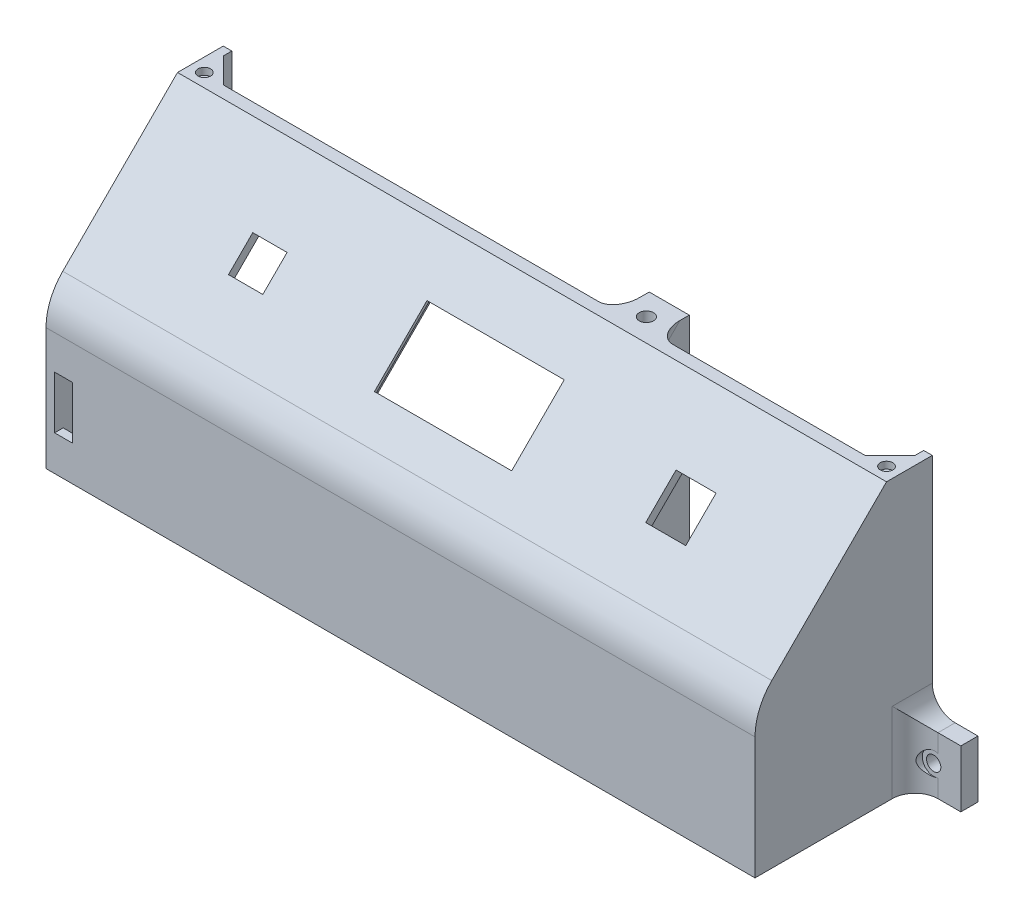
SolidWorks part; units mm, degrees
ref_plane "Front Plane" through (0, 0, 0) normal (0, 0, 1) x (1, 0, 0)
ref_plane "Top Plane" through (0, 0, 0) normal (0, 1, 0) x (1, 0, 0)
ref_plane "Right Plane" through (0, 0, 0) normal (1, 0, 0) x (0, 0, -1)
sketch "Sketch1" plane through (0, 0, 0) normal (0, 1, 0) x (1, 0, 0)
  line L1 (0, 31) -> (124, 31)
  line L2 (0, 31) -> (0, 0)
  line L3 (0, 0) -> (124, 0)
  line L4 (124, 31) -> (124, 0)
  dimension "D1" = 124
  dimension "30" = 31
extrude "Boss-Extrude1" add sketch "Sketch1" along normal blind 50
sketch "Sketch2" plane through (0, 0, 0) normal (-1, 0, 0) x (0, 0, 1)
  line L0 (-23, 48.5) -> (0, 25.5)
  line L2 (0, 50) -> (0, 0) construction
  line L3 (0, 25.5) -> (0, 50)
  line L5 (-31, 50) -> (-31, 0) construction
  line L7 (-31, 50) -> (0, 50)
  line L8 (-31, 50) -> (-31, 48.5)
  line L9 (-31, 48.5) -> (-23, 48.5)
  dimension "D1" = 45
  dimension "D2" = 1.5
  dimension "D4" = 8
extrude "Cut-Extrude1" cut sketch "Sketch2" against normal through all
ref_plane "Plane1" through (1.5, 0, 0) normal (-1, 0, 0) x (0, 0, 1)
sketch "Sketch3" plane through (1.5, 0, 0) normal (-1, 0, 0) x (0, 0, 1)
  line L0 (-31, 48.5) -> (-25.1213, 48.5)
  line L1 (-31, 48.5) -> (-31, 0) construction
  line L3 (-1.5, 24.8787) -> (-1.5, 1.5)
  line L4 (-1.5, 1.5) -> (-31, 1.5)
  line L5 (-31, 1.5) -> (-31, 48.5)
  line L6 (-31, 48.5) -> (-23, 48.5) construction
  line L8 (0, 25.5) -> (0, 0) construction
  line L9 (-31, 0) -> (0, 0) construction
  line L12 (-23, 48.5) -> (0, 25.5) construction
  line L14 (-23, 48.5) -> (0, 25.5) construction
  line L15 (-25.1213, 48.5) -> (-1.5, 24.8787)
  dimension "D1" = 1.5
  dimension "D3" = 1.5
  dimension "D4" = 1.5
extrude "Cut-Extrude2" cut sketch "Sketch3" against normal blind 121
sketch "Sketch4" plane through (0, 1.5, 0) normal (0, 1, 0) x (1, 0, 0)
  line L0 (84, 24) -> (84, 1.5)
  line L1 (122.5, 1.5) -> (1.5, 1.5) construction
  line L4 (122.5, 24) -> (84, 24)
  line L5 (84, 1.5) -> (81.5, 1.5)
  line L6 (81.5, 1.5) -> (81.5, 26.5)
  line L7 (81.5, 26.5) -> (122.5, 26.5)
  line L10 (8, 22) -> (1.5, 22) construction
  line L11 (60, 13.5) -> (60, 22)
  line L12 (60, 22) -> (29.5, 22)
  line L15 (27, 22) -> (27, 24.5)
  line L16 (27, 24.5) -> (62.5, 24.5)
  line L17 (62.5, 24.5) -> (62.5, 13.5)
  line L19 (29.5, 22) -> (27, 22)
  line L20 (60, 13.5) -> (62.5, 13.5)
  line L21 (1.5, 31) -> (1.5, 1.5) construction
  line L22 (29.5, 6.5) -> (27, 6.5)
  line L23 (29.5, 6.5) -> (29.5, 1.5)
  line L24 (29.5, 1.5) -> (27, 1.5)
  line L25 (27, 6.5) -> (27, 1.5)
  line L26 (62.5, 13.5) -> (81.5, 13.5) construction
  line L27 (27, 22) -> (8, 22) construction
  line L29 (122.5, 24) -> (122.5, 26.5)
  line L31 (122.5, 31) -> (122.5, 1.5) construction
  dimension "D1" = 2.5
  dimension "D2" = 2.5
  dimension "D3" = 38.5
  dimension "D4" = 22.5
  dimension "D5" = 6.5
  dimension "D6" = 30.5
  dimension "D7" = 20.5
  dimension "D8" = 2.5
  dimension "D9" = 2.5
  dimension "D10" = 12
  dimension "D11" = 2.5
  dimension "D12" = 5
  dimension "D13" = 2.5
extrude "Boss-Extrude2" add sketch "Sketch4" along normal blind 5
sketch "Sketch5" plane through (0, 12.75, 12.75) normal (0, 0.7071, 0.7071) x (1, 0, 0)
  line L0 (74, 28.5581) -> (124, 28.5581) construction
  line L1 (50, 41.5581) -> (74, 41.5581)
  line L2 (50, 41.5581) -> (50, 28.5581)
  line L3 (50, 28.5581) -> (74, 28.5581)
  line L4 (74, 41.5581) -> (74, 28.5581)
  line L5 (124, 50.5581) -> (124, 18.0312) construction
  line L6 (50, 28.5581) -> (0, 28.5581) construction
  line L7 (0, 50.5581) -> (0, 18.0312) construction
  line L8 (0, 50.5581) -> (0, 18.0312) construction
  line L9 (124, 50.5581) -> (0, 50.5581) construction
  line L14 (95.5, 31.3081) -> (102.5, 38.8081) construction
  line L19 (95.5, 38.8081) -> (102.5, 38.8081)
  line L20 (95.5, 38.8081) -> (95.5, 31.3081)
  line L21 (95.5, 31.3081) -> (102.5, 31.3081)
  line L22 (102.5, 38.8081) -> (102.5, 31.3081)
  line L23 (22, 32.0581) -> (28, 38.0581) construction
  line L24 (22, 38.0581) -> (28, 38.0581)
  line L25 (22, 38.0581) -> (22, 32.0581)
  line L26 (22, 32.0581) -> (28, 32.0581)
  line L27 (28, 38.0581) -> (28, 32.0581)
  line L28 (25, 35.0581) -> (50, 35.0581) construction
  line L29 (99, 35.0581) -> (74, 35.0581) construction
  line L30 (25, 35.0581) -> (0, 35.0581) construction
  point P22 (99, 35.0581)
  point P25 (25, 35.0581)
  point P26 (50, 35.0581)
  dimension "D3" = 6.5
  dimension "D4" = 6
  dimension "D6" = 7.5
  dimension "D1" = 24
  dimension "D2" = 13
  dimension "D5" = 6
  dimension "D7" = 7
  dimension "D8" = 9
extrude "Cut-Extrude3" cut sketch "Sketch5" against normal blind 4
sketch "Sketch6" plane through (0, 1.5, 0) normal (0, 1, 0) x (1, 0, 0)
  line L0 (27, 1.5) -> (1.5, 1.5) construction
  line L1 (9.4, 1.5) -> (5.9, 1.5)
  line L2 (9.4, 1.5) -> (9.4, 20.5)
  line L3 (9.4, 20.5) -> (5.9, 20.5)
  line L4 (5.9, 1.5) -> (5.9, 20.5)
  line L5 (1.5, 31) -> (1.5, 1.5) construction
  dimension "D1" = 3.5
  dimension "D2" = 4.4
  dimension "D3" = 19
extrude "Boss-Extrude3" add sketch "Sketch6" along normal blind 3.5
sketch "Sketch8" plane through (0, 5, 0) normal (0, 1, 0) x (1, 0, 0)
  line L0 (9.4, 1.5) -> (9.4, 20.5) construction
  line L1 (9.4, 9.5) -> (7.2, 9.5)
  line L2 (9.4, 9.5) -> (9.4, 18.5)
  line L3 (9.4, 18.5) -> (7.2, 18.5)
  line L4 (7.2, 9.5) -> (7.2, 18.5)
  line L5 (5.9, 1.5) -> (9.4, 1.5) construction
  dimension "D1" = 8
  dimension "D2" = 17
  dimension "D3" = 2.2
extrude "Boss-Extrude4" add sketch "Sketch8" along normal blind 8
fillet "Fillet1" radius 3 9 edges at (81.5, 1.5, -14) (27, 1.5, -4) (27, 1.5, -23.25) (44.75, 1.5, -24.5) (62.5, 1.5, -19) (102, 1.5, -26.5) (9.4, 1.5, -11) (8.3, 5, -9.5) (8.3, 5, -18.5)
sketch "Sketch7" plane through (0, 0, -1.5) normal (0, 0, -1) x (-1, 0, 0)
  line L0 (-1.5, -17.05) -> (-1.5, 17.05) construction
  line L1 (-4.6, 15.37) -> (-1.5, 15.37)
  line L2 (-4.6, 15.37) -> (-4.6, 6.17)
  line L3 (-4.6, 6.17) -> (-1.5, 6.17)
  line L4 (-1.5, 15.37) -> (-1.5, 6.17)
  line L5 (-122.5, 1.5) -> (-1.5, 1.5) construction
  dimension "D1" = 3.1
  dimension "D2" = 9.2
  dimension "D3" = 4.67
extrude "Cut-Extrude4" cut sketch "Sketch7" against normal blind 8
sketch "Sketch10" plane through (0, 0, -31) normal (0, 0, -1) x (-1, 0, 0)
  line L1 (-124, 10) -> (-132, 10)
  line L2 (-124, 10) -> (-124, 0)
  line L3 (-124, 0) -> (-132, 0)
  line L4 (-132, 10) -> (-132, 0)
  line L5 (0, 0) -> (8, 0)
  line L6 (0, 0) -> (0, 10)
  line L7 (0, 10) -> (8, 10)
  line L8 (8, 0) -> (8, 10)
  line L9 (-124, 0) -> (0, 0) construction
  dimension "D1" = 8
  dimension "D2" = 8
  dimension "D3" = 10
extrude "Boss-Extrude5" add sketch "Sketch10" against normal blind 3
fillet "Fillet4" radius 4 4 edges at (0, 5, -28) (124, 5, -28) (0, 10, -29.5) (124, 10, -29.5)
sketch "Sketch13" plane through (0, 0, -31) normal (0, 0, -1) x (-1, 0, 0)
  line L3 (-130.5, 8.5) -> (-124, 1.5) construction
  line L7 (0, 14) -> (0, 1.5) construction
  line L8 (6.5, 8.5) -> (0, 1.5) construction
  line L9 (8, 0) -> (8, 10) construction
  line L10 (8, 10) -> (4, 10) construction
  line L12 (-132, 0) -> (8, 0) construction
  line L14 (-122.5, 48.5) -> (-122.5, 1.5) construction
  line L15 (-128, 10) -> (-132, 10) construction
  line L16 (-132, 10) -> (-132, 0) construction
  circle A0 centre (3.25, 5) radius 1.25
  circle A1 centre (-127.25, 5) radius 1.25
  dimension "D3" = 2.5
  dimension "D9" = 2.5
  dimension "D1" = 1.5
  dimension "D2" = 1.5
  dimension "D4" = 1.5
  dimension "D5" = 1.5
  dimension "D6" = 1.5
  dimension "D7" = 1.5
  dimension "D8" = 1.5
extrude "Cut-Extrude6" cut sketch "Sketch13" against normal blind 5
sketch "Sketch14" plane through (0, 0, -28) normal (0, 0, 1) x (1, 0, 0)
  arc A0 (-4, 6) -> (-4, 4) centre (-3.25, 5) ccw construction
  arc A1 (-4, 6) -> (-4, 4) centre (-3.25, 5) ccw construction
  circle A2 centre (-3.25, 5) radius 2
  arc A3 (128, 4) -> (128, 6) centre (127.25, 5) ccw construction
  arc A4 (128, 4) -> (128, 6) centre (127.25, 5) ccw construction
  circle A5 centre (127.25, 5) radius 2
  dimension "D1" = 4
  dimension "D2" = 4
extrude "Cut-Extrude7" cut sketch "Sketch14" along normal blind 5
sketch "Sketch17" plane through (0, 1.5, 0) normal (0, 1, 0) x (1, 0, 0)
  line L4 (74.5, 24) -> (74.5, 31)
  line L5 (81.5, 26.5) -> (81.5, 1.5) construction
  line L6 (122.5, 31) -> (1.5, 31) construction
  line L7 (81.5, 24) -> (74.5, 24)
  line L8 (81.5, 24) -> (81.5, 31)
  line L9 (81.5, 31) -> (74.5, 31)
  line L11 (62.5, 13.5) -> (62.5, 24.5) construction
  line L12 (81.5, 26.5) -> (81.5, 1.5) construction
  line L13 (62.5, 13.5) -> (62.5, 24.5) construction
  line L14 (124, 24) -> (0, 24) construction
  dimension "D1" = 7
  dimension "D2" = 7
extrude "Boss-Extrude7" add sketch "Sketch17" along normal through all
sketch "Sketch18" plane through (0, 48.5, 0) normal (0, 1, 0) x (1, 0, 0)
  line L0 (81.5, 25.1213) -> (81.5, 31) construction
  line L1 (124, 23) -> (0, 23) construction
  line L2 (81.5, 31) -> (74.5, 31) construction
  line L3 (81.5, 25.1213) -> (81.5, 31) construction
  line L4 (124, 23) -> (0, 23) construction
  line L5 (81.5, 31) -> (74.5, 31) construction
  line L6 (74.5, 31) -> (81.5, 23) construction
  line L7 (81.5, 25.1213) -> (81.5, 23) construction
  circle A0 centre (78, 27) radius 1.25
  dimension "D1" = 2.5
extrude "Cut-Extrude9" cut sketch "Sketch18" against normal blind 5
fillet "Fillet5" radius 3 6 edges at (74.5, 47.9393, -24.5607) (81.5, 47.9393, -24.5607) (81.5, 5.5, -24) (80.6213, 2.3787, -24) (76.5, 1.5, -24) (74.5, 1.5, -27.5)
fillet "Fillet6" radius 10 1 edges at (62, 25.5, 0)
fillet "Fillet8" radius 3 2 edges at (62, 24.8787, -1.5) (122.5, 36.6893, -13.3107)
sketch "Sketch19" plane through (0, 11.6893, 11.6893) normal (0, -0.7071, -0.7071) x (1, 0, 0)
  line L0 (74, -41.5581) -> (50, -41.5581) construction
  line L1 (74.5, -41.5581) -> (68, -41.5581)
  line L2 (74.5, -41.5581) -> (74.5, -24.5581)
  line L3 (74.5, -24.5581) -> (68.5, -24.5581)
  line L4 (49.5, -41.5581) -> (49.5, -24.5581)
  line L5 (74, -28.5581) -> (74.5, -24.5581) construction
  line L6 (50, -28.5581) -> (49.5, -24.5581) construction
  line L7 (68.5, -24.5581) -> (68.5, -19.8952)
  line L9 (55.5, -19.8952) -> (55.5, -24.5581)
  line L10 (55.5, -24.5581) -> (49.5, -24.5581)
  line L12 (55.5, -19.8952) -> (68.5, -19.8952)
  line L13 (68, -41.5581) -> (68, -46.5581)
  line L14 (68, -46.5581) -> (56, -46.5581)
  line L15 (56, -46.5581) -> (56, -41.5581)
  line L16 (56, -41.5581) -> (49.5, -41.5581)
  line L18 (119.5, -19.8952) -> (1.5, -19.8952) construction
  dimension "D1" = 17
  dimension "D2" = 25
  dimension "D3" = 13
  dimension "D5" = 12
  dimension "D6" = 5
extrude "Cut-Extrude10" cut sketch "Sketch19" against normal blind 1
sketch "Sketch21" plane through (0, 1.5, 0) normal (0, 1, 0) x (1, 0, 0)
  line L0 (1.5, 31) -> (1.5, 1.5) construction
  line L1 (1.5, 26) -> (5.9, 26)
  line L2 (1.5, 26) -> (1.5, 31)
  line L3 (1.5, 31) -> (5.9, 31)
  line L4 (5.9, 26) -> (5.9, 31)
  line L6 (71.5, 31) -> (1.5, 31) construction
  dimension "D2" = 5
  dimension "D3" = 4.4
extrude "Boss-Extrude8" add sketch "Sketch21" along normal blind 2
sketch "Sketch22" plane through (1.5, 0, 0) normal (1, 0, 0) x (0, 0, -1)
  line L0 (26, 1.5) -> (1.5, 1.5) construction
  line L1 (17.2, 1.5) -> (17.8, 1.5)
  line L2 (13.5, 5.2) -> (13.5, 21.8)
  line L3 (17.2, 25.5) -> (17.8, 25.5)
  line L4 (21.5, 5.2) -> (21.5, 21.8)
  line L6 (1.5, 1.5) -> (1.5, 6.17) construction
  arc A0 (17.8, 1.5) -> (21.5, 5.2) centre (17.8, 5.2) ccw
  arc A1 (17.2, 1.5) -> (13.5, 5.2) centre (17.2, 5.2) cw
  arc A2 (13.5, 21.8) -> (17.2, 25.5) centre (17.2, 21.8) cw
  arc A3 (17.8, 25.5) -> (21.5, 21.8) centre (17.8, 21.8) cw
  point P11 (21.5, 1.5)
  point P14 (13.5, 1.5)
  point P19 (21.5, 25.5)
  dimension "D3" = 3.7
  dimension "D1" = 12
  dimension "D2" = 24
  dimension "D4" = 20
extrude "Cut-Extrude12" cut sketch "Sketch22" against normal blind 8
sketch "Sketch23" plane through (0, 1.5, 0) normal (0, 1, 0) x (1, 0, 0)
  line L0 (122.5, 1.5) -> (84, 1.5) construction
  line L1 (117.5, 4.5) -> (89, 4.5)
  line L2 (119.5, 6.5) -> (119.5, 19)
  line L3 (117.5, 21) -> (89, 21)
  line L4 (87, 6.5) -> (87, 19)
  line L5 (84, 1.5) -> (84, 24) construction
  line L6 (84, 24) -> (122.5, 24) construction
  line L7 (122.5, 24) -> (122.5, 1.5) construction
  line L8 (24, 21) -> (24, 25.5)
  line L13 (55, 4.5) -> (34.5, 4.5)
  line L14 (57, 6.5) -> (57, 17)
  line L15 (55, 19) -> (31.4185, 19)
  line L16 (32.5, 6.5) -> (32.5, 7.5)
  line L17 (30.5, 9.5) -> (26, 9.5)
  line L19 (31.4185, 19) -> (26, 19)
  line L21 (24, 4.5) -> (16.4, 4.5)
  line L22 (24, 4.5) -> (24, 7.5)
  line L23 (22, 27.5) -> (16.4, 27.5)
  line L24 (14.4, 6.5) -> (14.4, 25.5)
  line L25 (24, 1.5) -> (12.4, 1.5) construction
  line L26 (78.5, 1.5) -> (29.5, 1.5) construction
  line L27 (29.5, 6.5) -> (24, 6.5) construction
  line L28 (24, 22) -> (60, 22) construction
  line L29 (60, 22) -> (60, 13.5) construction
  line L30 (29.5, 1.5) -> (29.5, 6.5) construction
  line L32 (9.4, 1.5) -> (9.4, 20.5) construction
  line L33 (16.4, 4.5) -> (14.4, 6.5)
  line L34 (24, 27.5) -> (65.5, 27.5) construction
  line L35 (16.4, 27.5) -> (14.4, 25.5)
  line L36 (26, 9.5) -> (24, 7.5)
  line L37 (32.5, 7.5) -> (30.5, 9.5)
  line L38 (34.5, 4.5) -> (32.5, 6.5)
  line L39 (57, 6.5) -> (55, 4.5)
  line L40 (57, 17) -> (55, 19)
  line L41 (26, 19) -> (24, 21)
  line L42 (24, 25.5) -> (22, 27.5)
  line L43 (89, 4.5) -> (87, 6.5)
  line L44 (119.5, 6.5) -> (117.5, 4.5)
  line L45 (119.5, 19) -> (117.5, 21)
  line L46 (89, 21) -> (87, 19)
  line L47 (78.5, 21) -> (71.5, 21) construction
  line L48 (73.5, 18) -> (67.5, 18)
  line L49 (75.5, 16) -> (75.5, 6.5)
  line L50 (73.5, 4.5) -> (67.5, 4.5)
  line L51 (65.5, 16) -> (65.5, 6.5)
  line L52 (78.5, 1.5) -> (78.5, 21) construction
  line L53 (65.5, 27.5) -> (65.5, 13.5) construction
  line L54 (67.5, 18) -> (65.5, 16)
  line L55 (67.5, 4.5) -> (65.5, 6.5)
  line L56 (75.5, 6.5) -> (73.5, 4.5)
  line L57 (75.5, 16) -> (73.5, 18)
  line L58 (24, 1.5) -> (24, 6.5) construction
  point P0 (119.5, 4.5)
  point P1 (87, 21)
  point P2 (119.5, 21)
  point P3 (87, 4.5)
  point P12 (57, 4.5)
  point P14 (57, 19)
  point P15 (32.5, 4.5)
  point P16 (32.5, 9.5)
  point P17 (24, 19)
  point P19 (24, 9.5)
  point P21 (14.4, 27.5)
  point P22 (24, 27.5)
  point P23 (14.4, 4.5)
  point P67 (75.5, 18)
  point P68 (65.5, 4.5)
  point P69 (75.5, 4.5)
  point P70 (65.5, 18)
  dimension "D1" = 3
  dimension "D2" = 3
  dimension "D3" = 3
  dimension "D4" = 3
  dimension "D5" = 3
  dimension "D6" = 3
  dimension "D7" = 3
  dimension "D8" = 3
  dimension "D9" = 3
  dimension "D10" = 3
  dimension "D12" = 5
  dimension "D13" = 3
  dimension "D14" = 3
  dimension "D15" = 3
extrude "Cut-Extrude13" cut sketch "Sketch23" against normal blind 1
sketch "Sketch24" plane through (0, 48.5, 0) normal (0, 1, 0) x (1, 0, 0)
  line L0 (124, 23) -> (0, 23) construction
  line L2 (0, 31) -> (0, 23)
  line L3 (0, 23) -> (8, 23)
  line L5 (0, 31) -> (8, 23)
  dimension "D1" = 8
ref_plane "Plane2" through (0, 23.636, 0) normal (0, 1, 0) x (1, 0, 0)
sketch "Sketch25" plane through (0, 23.636, 0) normal (0, 1, 0) x (1, 0, 0)
  line L0 (0, 23) -> (0, 0) construction
  line L1 (0, 0.3209) -> (1.5, 0.3209)
  line L2 (0, 0.3209) -> (0, 1.5)
  line L24 (124, 0) -> (0, 0) construction
  line L25 (0, 1.5) -> (1.5, 0.3209)
  dimension "D1" = 1.5
  dimension "D2" = 0.3209
  dimension "D3" = 1.1791
loft "Loft2" add profiles "Sketch25", "Sketch24" connector at (1.5, 23.636, -0.3209) connector at (8, 48.5, -23)
sketch "Sketch26" plane through (0, 48.5, 0) normal (0, 1, 0) x (1, 0, 0)
  line L0 (5.8787, 25.1213) -> (1.5, 29.5) construction
  line L1 (5.8787, 25.1213) -> (1.5, 29.5) construction
  line L2 (2.3431, 25.3431) -> (4, 27) construction
  line L3 (2.3431, 25.3431) -> (0, 25.3431) construction
  line L4 (0, 31) -> (0, 23) construction
  line L5 (2.3431, 25.3431) -> (2.3431, 23) construction
  line L6 (124, 23) -> (0, 23) construction
  circle A0 centre (2.3431, 25.3431) radius 1.1
  dimension "D1" = 2.2
extrude "Cut-Extrude14" cut sketch "Sketch26" against normal blind 1.2 contours A0
ref_plane "Plane3" through (62, 0, 0) normal (1, 0, 0) x (0, 0, -1)
mirror "Mirror1" about plane through (62, 0, 0) normal (1, 0, 0) of "Cut-Extrude14", "Loft2"
fillet "Fillet10" radius 1.2 1 edges at (78, 47.3787, -24)
